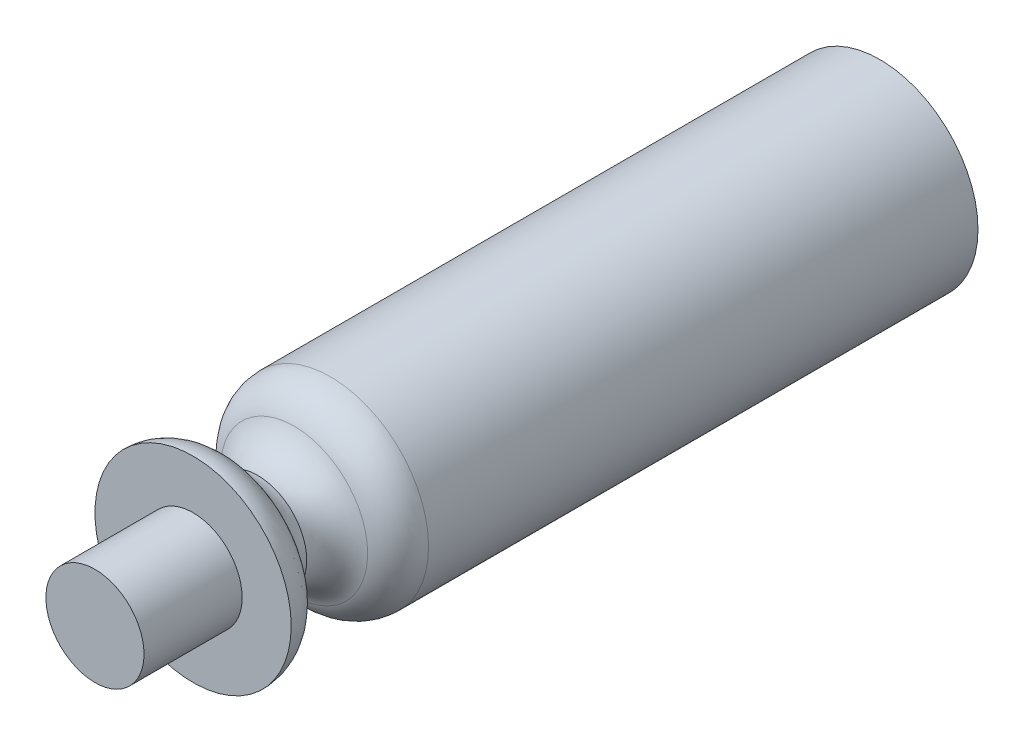
SolidWorks part; units mm, degrees
ref_plane "Спереди" through (0, 0, 0) normal (0, 0, 1) x (1, 0, 0)
ref_plane "Сверху" through (0, 0, 0) normal (0, 1, 0) x (1, 0, 0)
ref_plane "Справа" through (0, 0, 0) normal (1, 0, 0) x (0, 0, -1)
sketch "Эскиз1" plane through (0, 0, 0) normal (0, 0, 1) x (1, 0, 0)
  circle A0 centre (0, 0) radius 5
extrude "Бобышка-Вытянуть1" add sketch "Эскиз1" along normal blind 40
sketch "Эскиз3" plane through (0, 0, 0) normal (0, 0, -1) x (-1, 0, 0)
  line L0 (0, 4.0104) -> (0, -5.6161) construction
  line L1 (2.2, 4.0104) -> (2.2, -5.6161) construction
  line L2 (-2.2, -5.4288) -> (-2.2, 4.4787) construction
  line L3 (-2.2, -2.3238) -> (-2.2, 2.3238)
  line L4 (2.2, 2.3238) -> (2.2, -2.3238)
  arc A0 (-2.2, -2.3238) -> (2.2, -2.3238) centre (0, 0) ccw
  arc A1 (2.2, 2.3238) -> (-2.2, 2.3238) centre (0, 0) ccw
  dimension "D1" = 2.2
  dimension "D2" = 2.2
extrude "Вырез-Вытянуть1" cut sketch "Эскиз3" against normal blind 7
sketch "Эскиз4" plane through (0, 0, 40) normal (0, 0, 1) x (1, 0, 0)
  circle A0 centre (0, 0) radius 2.5
extrude "Вырез-Вытянуть-Тонкостенный4" cut sketch "Эскиз4" against normal blind 10 thin thin type one direction wall 4
sketch "Эскиз7" plane through (0, 0, 40) normal (0, 0, 1) x (1, 0, 0)
  circle A0 centre (0, 0) radius 5
extrude "Бобышка-Вытянуть2" add sketch "Эскиз7" against normal blind 7
sketch "Эскиз10" plane through (0, 0, 40) normal (0, 0, 1) x (1, 0, 0)
  circle A0 centre (0, 0) radius 2.5
extrude "Вырез-Вытянуть-Тонкостенный5" cut sketch "Эскиз10" against normal blind 5 thin thin type one direction wall 4
fillet "Скругление3" radius 2 1 edges at (5, 0, 30)
fillet "Скругление4" radius 2 1 edges at (5, 0, 33)
fillet "Скругление5" radius 2 1 edges at (2.5, 0, 30)
fillet "Скругление6" radius 2 1 edges at (2.5, 0, 33)
equation "\"D2@Эскиз3\"=\"D1@Эскиз3\""
